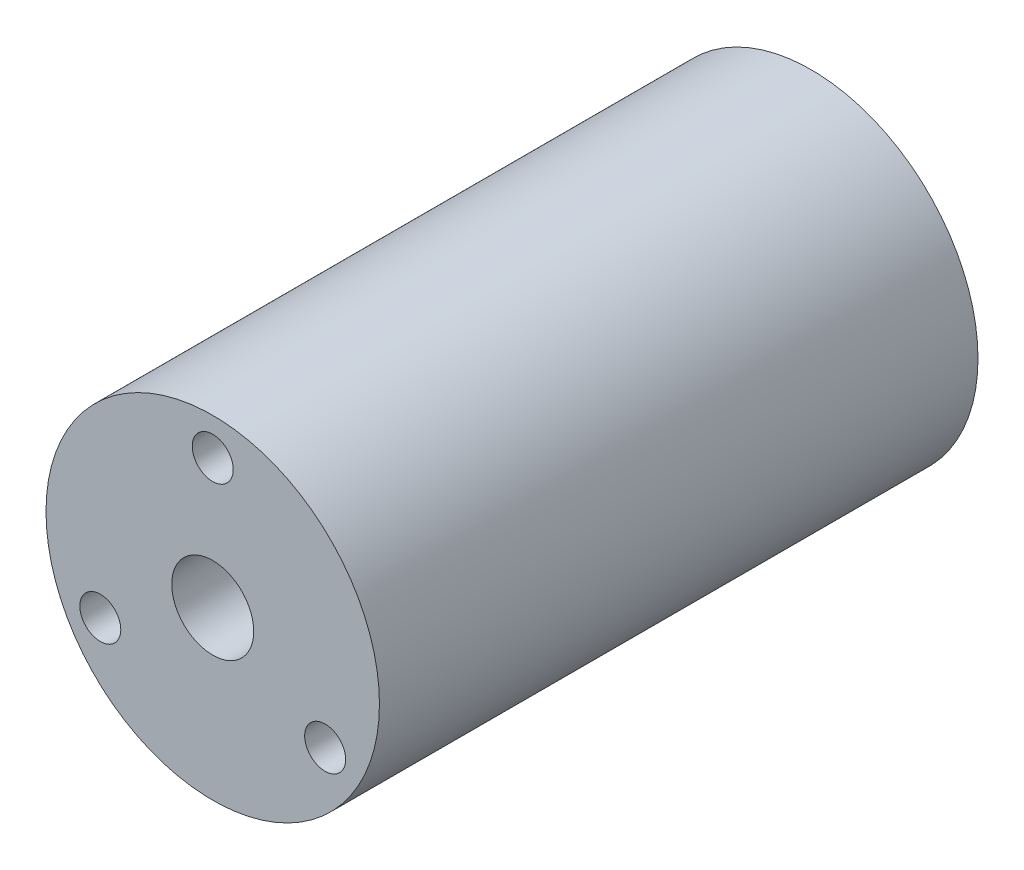
SolidWorks part; units mm, degrees
ref_plane "前视基准面" through (0, 0, 0) normal (0, 0, 1) x (1, 0, 0)
ref_plane "上视基准面" through (0, 0, 0) normal (0, 1, 0) x (1, 0, 0)
ref_plane "右视基准面" through (0, 0, 0) normal (1, 0, 0) x (0, 0, -1)
sketch "草图1" plane through (0, 0, 0) normal (0, 0, 1) x (1, 0, 0)
  circle A0 centre (0, 0) radius 12.2
  circle A1 centre (0, 0) radius 3
extrude "凸台-拉伸1" add sketch "草图1" against normal blind 43.8
sketch "草图2" plane through (0, 0, 0) normal (0, 0, 1) x (1, 0, 0)
  line L0 (0, 0) -> (0, 9.5)
  line L1 (0, 0) -> (8.2272, -4.75)
  line L2 (0, 0) -> (-8.2272, -4.75)
  circle A0 centre (0, 0) radius 9.5
  circle A1 centre (0, 9.5) radius 1.5
  circle A2 centre (8.2272, -4.75) radius 1.5
  circle A3 centre (-8.2272, -4.75) radius 1.5
  point P9 (0, 0)
  point P15 (0, 0)
  dimension "D1" = 3
  dimension "D2" = 3
extrude "切除-拉伸1" cut sketch "草图2" against normal blind 5.5 contours A1
ref_axis "基准轴1" through (0, 0, -43.8) along (0, 0, 1)
pattern_circular "阵列(圆周)2" count 3 every 120 about axis through (0, 0, -43.8) along (0, 0, 1) of "切除-拉伸1"
